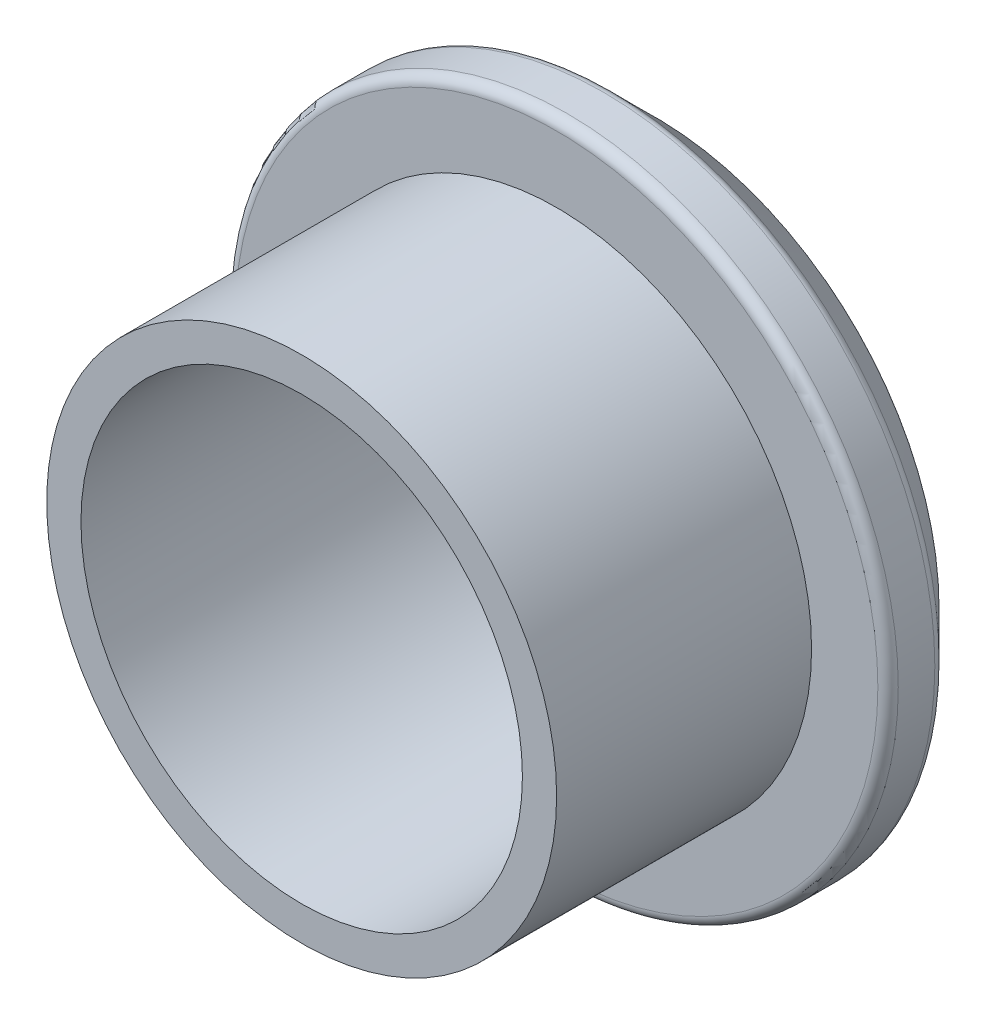
SolidWorks part; units mm, degrees
material "moto_black"
ref_plane "Front Plane" through (0, 0, 0) normal (0, 0, 1) x (1, 0, 0)
ref_plane "Top Plane" through (0, 0, 0) normal (0, 1, 0) x (1, 0, 0)
ref_plane "Right Plane" through (0, 0, 0) normal (1, 0, 0) x (0, 0, -1)
sketch "Sketch1" plane through (0, 0, 0) normal (0, 0, 1) x (1, 0, 0)
  circle A0 centre (0, 0) radius 10
  circle A1 centre (0, 0) radius 13
  circle A2 centre (0, 0) radius 8.6579
  dimension "D1" = 20
  dimension "D2" = 3
extrude "Boss-Extrude1" add sketch "Sketch1" along normal blind 10 contours A0 A2 region at (-9.7172, 0, 0)
extrude "Boss-Extrude2" add sketch "Sketch1<3>" against normal blind 4 contours A1 A0 | A0 A2 region at (-9.7172, 0, 0) region at (-12.6323, 0, 0)
sketch "Sketch1<3>" plane through (0, 0, 0) normal (0, 0, 1) x (1, 0, 0) same geometry as "Sketch1"
chamfer "Chamfer1" distance 2 angle 45 1 edges at (13, 0, -4)
fillet "Fillet1" radius 0.4 1 edges at (8.6579, 0, -4)
fillet "Fillet2" radius 0.4 2 edges at (13, 0, -2) (11, 0, -4)
fillet "Fillet3" radius 0.4 1 edges at (13, 0, 0)
